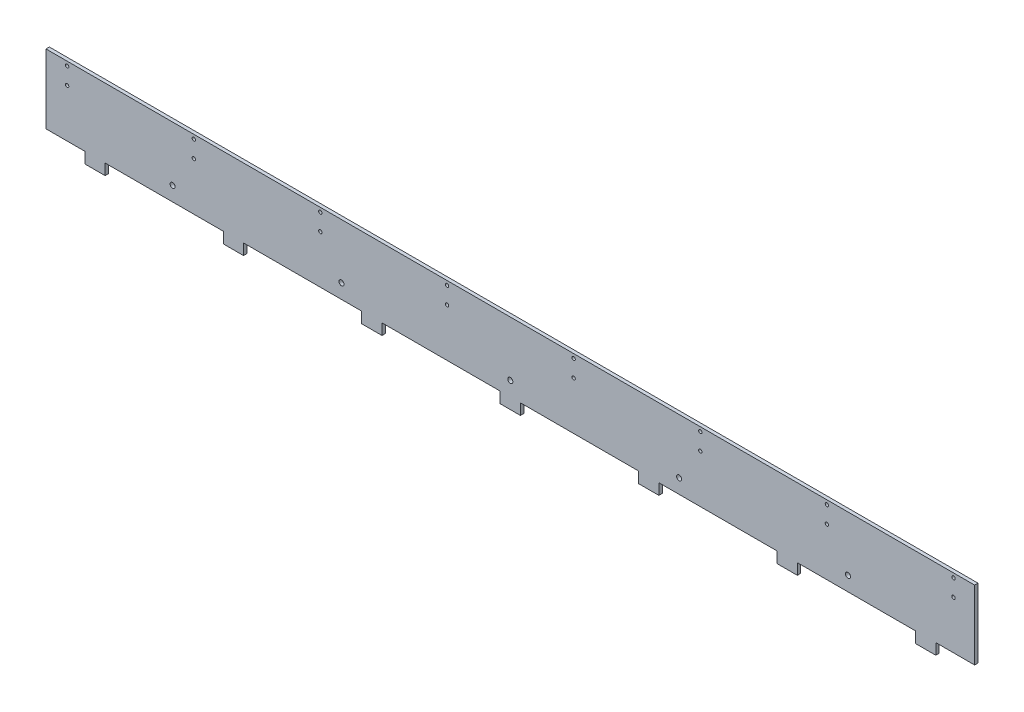
SolidWorks part; units mm, degrees
ref_plane "Спереди" through (0, 0, 0) normal (0, 0, 1) x (1, 0, 0)
ref_plane "Сверху" through (0, 0, 0) normal (0, 1, 0) x (1, 0, 0)
ref_plane "Справа" through (0, 0, 0) normal (1, 0, 0) x (0, 0, -1)
sketch "Эскиз1" plane through (0, 0, 0) normal (0, 0, 1) x (1, 0, 0)
  line L1 (-550, -47.5) -> (550, -47.5)
  line L2 (-550, -47.5) -> (-550, 47.5)
  line L3 (-550, 47.5) -> (550, 47.5)
  line L4 (550, -47.5) -> (550, 47.5)
  line L5 (0, 47.5) -> (0, -47.5) construction
  line L6 (-550, 0) -> (550, 0) construction
  point P0 (0, 0)
  dimension "D1" = 95
  dimension "D2" = 1100
extrude "Бобышка-Вытянуть1" add sketch "Эскиз1" along normal mid plane 4
sketch "Эскиз2" plane through (0, 0, 2) normal (0, 0, 1) x (1, 0, 0)
  line L0 (-550, -47.5) -> (550, -47.5) construction
  line L1 (-550, -47.5) -> (-504, -47.5)
  line L2 (-550, -47.5) -> (-550, -34.5)
  line L3 (-550, -34.5) -> (-504, -34.5)
  line L4 (-504, -47.5) -> (-504, -34.5)
  line L5 (550, -47.5) -> (504, -47.5)
  line L6 (550, -47.5) -> (550, -34.5)
  line L7 (550, -34.5) -> (504, -34.5)
  line L8 (504, -47.5) -> (504, -34.5)
  line L9 (-480, -34.5) -> (-340, -34.5)
  line L10 (-480, -34.5) -> (-480, -47.5)
  line L11 (-480, -47.5) -> (-340, -47.5)
  line L12 (-340, -34.5) -> (-340, -47.5)
  line L14 (-316, -34.5) -> (-176, -34.5)
  line L15 (-316, -34.5) -> (-316, -47.5)
  line L16 (-316, -47.5) -> (-176, -47.5)
  line L17 (-176, -34.5) -> (-176, -47.5)
  line L18 (-152, -34.5) -> (-12, -34.5)
  line L19 (-152, -34.5) -> (-152, -47.5)
  line L20 (-152, -47.5) -> (-12, -47.5)
  line L21 (-12, -34.5) -> (-12, -47.5)
  line L22 (12, -34.5) -> (152, -34.5)
  line L23 (12, -34.5) -> (12, -47.5)
  line L24 (12, -47.5) -> (152, -47.5)
  line L25 (152, -34.5) -> (152, -47.5)
  line L26 (176, -34.5) -> (316, -34.5)
  line L27 (176, -34.5) -> (176, -47.5)
  line L28 (176, -47.5) -> (316, -47.5)
  line L29 (316, -34.5) -> (316, -47.5)
  line L30 (340, -34.5) -> (480, -34.5)
  line L31 (340, -34.5) -> (340, -47.5)
  line L32 (340, -47.5) -> (480, -47.5)
  line L33 (480, -34.5) -> (480, -47.5)
  point P20 (-316, -41)
  point P25 (-152, -41)
  point P26 (152, -41)
  point P39 (340, -41)
  dimension "D1" = 13
  dimension "D5" = 24
  dimension "D6" = 140
  dimension "D7" = 24
  dimension "D2" = 24
  dimension "D3" = 140
  dimension "D4" = 140
  dimension "D8" = 24
  dimension "D9" = 140
  dimension "D10" = 24
  dimension "D11" = 140
  dimension "D12" = 24
  dimension "D13" = 140
  dimension "D14" = 24
extrude "Вырез-Вытянуть1" cut sketch "Эскиз2" against normal through all
sketch "Эскиз3" plane through (0, 0, 2) normal (0, 0, 1) x (1, 0, 0)
  line L0 (550, 47.5) -> (-550, 47.5) construction
  line L1 (-550, 47.5) -> (-550, -34.5) construction
  circle A0 centre (-525, 42.5) radius 2
  circle A1 centre (-525, 22.5) radius 2
  point P8 (0, 0)
  dimension "D1" = 4
  dimension "D2" = 5
  dimension "D3" = 20
  dimension "D4" = 25
extrude "Вырез-Вытянуть2" cut sketch "Эскиз3" against normal through all
pattern_linear "Линейный массив1" count 8 spacing 150 along (1, 0, 0) of "Вырез-Вытянуть2"
sketch "Эскиз4" plane through (0, 0, -2) normal (0, 0, -1) x (-1, 0, 0)
  circle A1 centre (-400, -17.5) radius 3
  circle A2 centre (-400, -17.5) radius 3
  dimension "D1" = 0
extrude "Вырез-Вытянуть3" cut sketch "Эскиз4" against normal through all
pattern_linear "Линейный массив2" count 5 spacing 200 along (-1, 0, 0) of "Вырез-Вытянуть3"
equation "\"D7@Эскиз2\"=\"D5@Эскиз2\""
equation "\"D2@Эскиз2\"=\"D5@Эскиз2\""
equation "\"D3@Эскиз2\"=\"D6@Эскиз2\""
equation "\"D4@Эскиз2\"=\"D6@Эскиз2\""
equation "\"D8@Эскиз2\"=\"D5@Эскиз2\""
equation "\"D9@Эскиз2\"=\"D6@Эскиз2\""
equation "\"D10@Эскиз2\"=\"D5@Эскиз2\""
equation "\"D11@Эскиз2\"=\"D6@Эскиз2\""
equation "\"D12@Эскиз2\"=\"D5@Эскиз2\""
equation "\"D13@Эскиз2\"=\"D6@Эскиз2\""
equation "\"D14@Эскиз2\"=\"D5@Эскиз2\""
